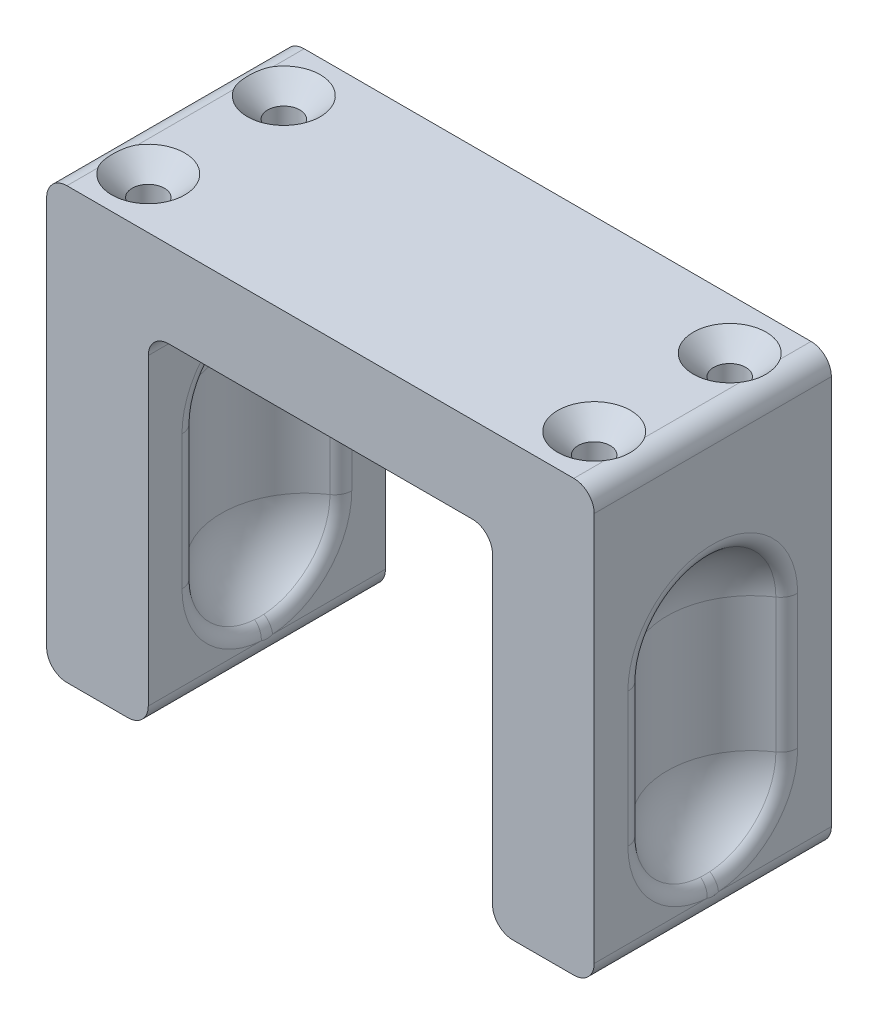
SolidWorks part; units mm, degrees
ref_plane "Front Plane" through (0, 0, 0) normal (0, 0, 1) x (1, 0, 0)
ref_plane "Top Plane" through (0, 0, 0) normal (0, 1, 0) x (1, 0, 0)
ref_plane "Right Plane" through (0, 0, 0) normal (1, 0, 0) x (0, 0, -1)
sketch "Sketch1" plane through (0, 0, 0) normal (0, 0, 1) x (1, 0, 0)
  line L1 (-25.4, -25.4) -> (25.4, -25.4)
  line L2 (-25.4, -25.4) -> (-25.4, 25.4)
  line L3 (-25.4, 25.4) -> (25.4, 25.4)
  line L4 (25.4, -25.4) -> (25.4, 25.4)
  line L5 (-25.4, -25.4) -> (25.4, 25.4) construction
  line L6 (-25.4, 25.4) -> (25.4, -25.4) construction
  point P0 (0, 0)
  dimension "D1" = 50.8
  dimension "D2" = 50.8
sketch "Sketch2" plane through (0, 0, 0) normal (0, 0, 1) x (1, 0, 0)
  line L0 (-25.4, 25.4) -> (25.4, 25.4) construction
  line L1 (0, 25.4) -> (25.4, 25.4)
  line L2 (25.4, 25.4) -> (25.4, -25.4)
  line L3 (25.4, -25.4) -> (40.4, -25.4)
  line L4 (40.4, -25.4) -> (40.4, 38.1)
  line L5 (40.4, 38.1) -> (0, 38.1)
  line L6 (0, 38.1) -> (0, 25.4)
  dimension "D1" = 63.5
  dimension "D2" = 15
extrude "Boss-Extrude1" add sketch "Sketch2" along normal mid plane 35
sketch "Sketch3" plane through (0, -25.4, 0) normal (0, -1, 0) x (1, 0, 0)
  line L0 (25.4, 17.5) -> (32.9, 10) construction
  line L1 (32.9, 10) -> (40.4, 17.5) construction
  line L2 (25.4, -17.5) -> (32.9, -10) construction
  line L3 (32.9, -10) -> (32.9, 10) construction
sketch "Sketch4" plane through (0, 38.1, 0) normal (0, 1, 0) x (1, 0, 0)
  circle A0 centre (32.9, 10) radius 2.375
  circle A1 centre (32.9, -10) radius 2.375
  point P0 (32.9, 10)
  point P1 (32.9, -10)
  dimension "D1" = 4.75
extrude "Cut-Extrude1" cut sketch "Sketch4" against normal through all
chamfer "Chamfer1" distance 3 angle 45 2 edges at (30.525, 38.1, 10) (30.525, 38.1, -10)
fillet "Fillet1" radius 3 4 edges at (40.4, 38.1, 0) (40.4, -25.4, 0) (25.4, -25.4, 0) (25.4, 25.4, 0)
ref_plane "Plane1" through (32.9, 0, 0) normal (-1, 0, 0) x (0, 0, 1)
sketch "Sketch5" plane through (0, 0, 0) normal (0, 0, 1) x (1, 0, 0)
  line L0 (19.65, 9.9) -> (19.65, -9.9) construction
  line L1 (32.15, 9.9) -> (32.15, -9.9) construction
  line L2 (7.15, 9.9) -> (7.15, -9.9) construction
  line L3 (32.9, 19.25) -> (32.9, -19.25) construction
  line L5 (19.65, 22.4) -> (0, 22.4) construction
  line L6 (0, 22.4) -> (0, 0) construction
  line L7 (-25.4, 25.4) -> (25.4, 25.4) construction
  line L8 (19.65, 22.4) -> (19.65, -22.4)
  line L9 (32.15, -9.9) -> (32.15, 9.9)
  arc A0 (32.15, 9.9) -> (7.15, 9.9) centre (19.65, 9.9) ccw construction
  arc A1 (7.15, -9.9) -> (32.15, -9.9) centre (19.65, -9.9) ccw construction
  arc A2 (19.65, 22.4) -> (32.15, 9.9) centre (19.65, 9.9) cw
  arc A3 (19.65, -22.4) -> (32.15, -9.9) centre (19.65, -9.9) ccw
  point P2 (19.65, 0)
  dimension "D1" = 25
  dimension "D2" = 0.75
  dimension "D3" = 3
revolve "Cut-Revolve3" cut sketch "Sketch5" angle 360 about L8
mirror "Mirror2" about plane through (32.9, 0, 0) normal (-1, 0, 0) of "Cut-Revolve3"
fillet "Fillet2" radius 2.5 8 edges at (40.4, 0, -11.099) (40.4, -20.999, 0) (40.4, 0, 11.099) (25.4, 0, 11.099) (25.4, -20.999, 0) (25.4, 0, -11.099) (40.4, 20.999, 0) (25.4, 20.999, 0)
mirror "Mirror1" about plane through (0, 38.1, 17.5) normal (1, 0, 0) of bodies 105 102
